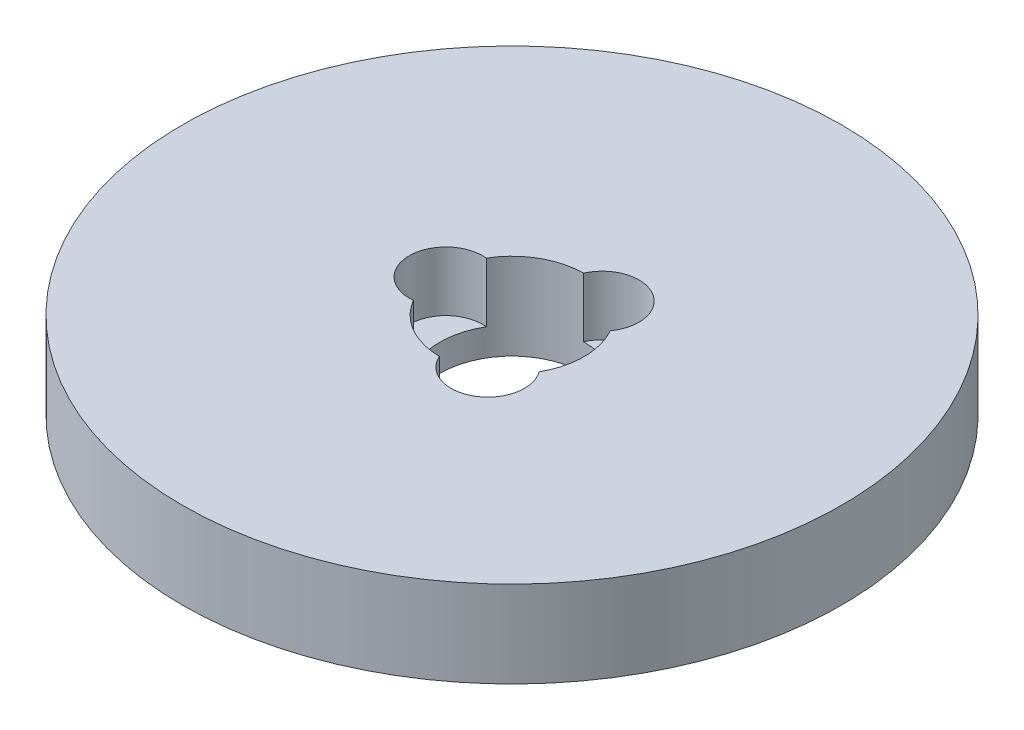
SolidWorks part; units mm, degrees
ref_plane "Front Plane" through (0, 0, 0) normal (0, 0, 1) x (1, 0, 0)
ref_plane "Top Plane" through (0, 0, 0) normal (0, 1, 0) x (1, 0, 0)
ref_plane "Right Plane" through (0, 0, 0) normal (1, 0, 0) x (0, 0, -1)
sketch "Sketch1" plane through (0, 0, 0) normal (0, 1, 0) x (1, 0, 0)
  circle A0 centre (0, 0) radius 80
  dimension "FLANGE_OD" = 160
extrude "Boss-Extrude1" add sketch "Sketch1" along normal blind 21
sketch "Sketch2" plane through (0, 0, 0) normal (0, 1, 0) x (1, 0, 0)
  circle A0 centre (0, 0) radius 17.5
  dimension "BORE_D" = 35
extrude "Cut-Extrude1" cut sketch "Sketch2" along normal through all
sketch "Sketch3" plane through (0, 21, 0) normal (0, 1, 0) x (1, 0, 0)
  circle A0 centre (0, 0) radius 16.0419 construction
  circle A1 centre (-16.0419, 0) radius 8.9113
  dimension "BOLT_D" = 17.8227
  dimension "BOLT_PCD" = 32.0839
extrude "Cut-Extrude2" cut sketch "Sketch3" against normal blind 14.434
pattern_circular "CirPattern1" count 3 over 360 about axis through (0, 0, 0) along (0, 1, 0) of "Cut-Extrude2"
